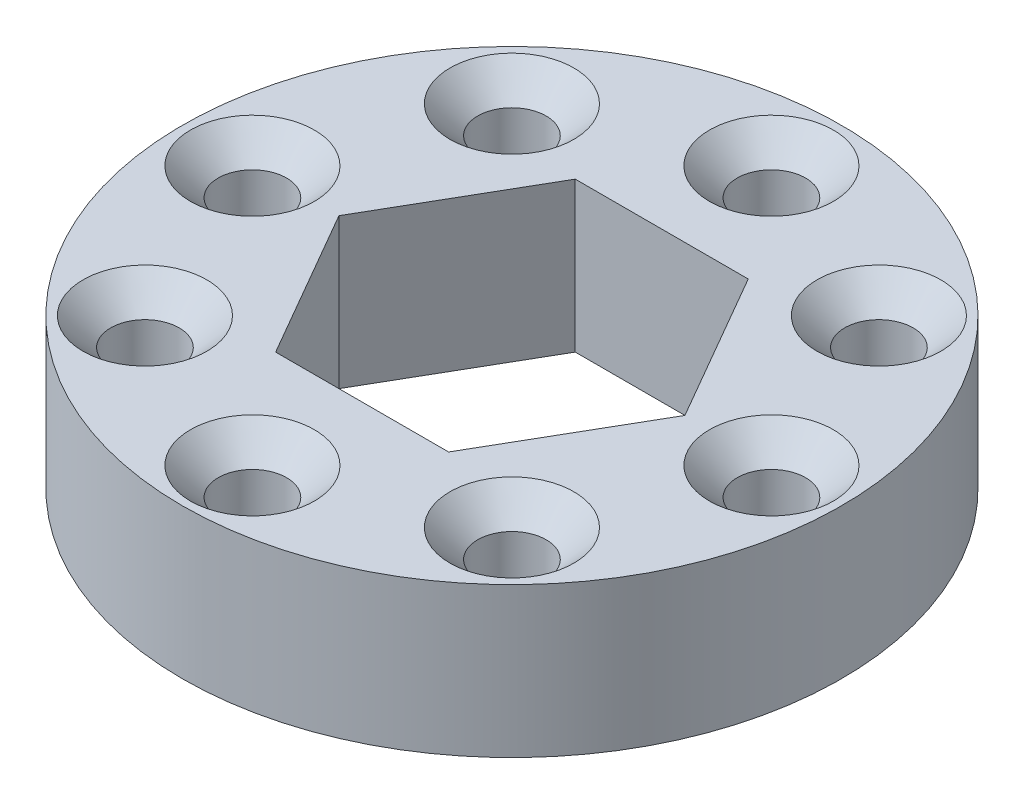
SolidWorks part; units mm, degrees
ref_plane "Front Plane" through (0, 0, 0) normal (0, 0, 1) x (1, 0, 0)
ref_plane "Top Plane" through (0, 0, 0) normal (0, 1, 0) x (1, 0, 0)
ref_plane "Right Plane" through (0, 0, 0) normal (1, 0, 0) x (0, 0, -1)
sketch "Sketch1" plane through (0, 0, 0) normal (0, 1, 0) x (1, 0, 0)
  line L1 (3.6662, 6.35) -> (-3.6662, 6.35)
  line L2 (-3.6662, 6.35) -> (-7.3323, 0)
  line L3 (-7.3323, 0) -> (-3.6662, -6.35)
  line L4 (-3.6662, -6.35) -> (3.6662, -6.35)
  line L5 (3.6662, -6.35) -> (7.3323, 0)
  line L6 (7.3323, 0) -> (3.6662, 6.35)
  circle A0 centre (0, 0) radius 13.97
  circle A1 centre (0, 0) radius 6.35 construction
  dimension "D1" = 27.94
  dimension "D2" = 12.7
extrude "Boss-Extrude1" add sketch "Sketch1" along normal mid plane 6.35
hole_wizard "M2.5 Clearance Hole1" positions "Sketch2" profile "Sketch3" hole size "M2.5" standard "ANSI Metric" end condition through all
sketch "Sketch2" plane through (0, 3.175, 0) normal (0, 1, 0) x (1, 0, 0)
  point P0 (0, 11)
  dimension "D1" = 11
sketch "Sketch3" plane through (0, 3.175, -11) normal (1, 0, 0) x (0, 0, 1)
  line L0 (0, 0) -> (0, 6.35)
  line L1 (0, 6.35) -> (1.45, 6.35)
  line L2 (1.45, 6.35) -> (1.45, 1.175)
  line L3 (1.45, 1.175) -> (2.625, 0)
  line L5 (2.625, 0) -> (0, 0)
  line L6 (-1.45, 1.175) -> (-2.625, 0) construction
  line L11 (0, -6.35) -> (0, 107.95) construction
  dimension "Thru Hole Dia." = 2.9
  dimension "Thru Hole Depth" = 6.35
  dimension "Near C'Sink Dia." = 5.25
  dimension "Near C'Sink Angle" = 90
pattern_circular "CirPattern1" count 8 over 360 about axis through (0, 3.175, 0) along (0, 1, 0) of "M2.5 Clearance Hole1"
